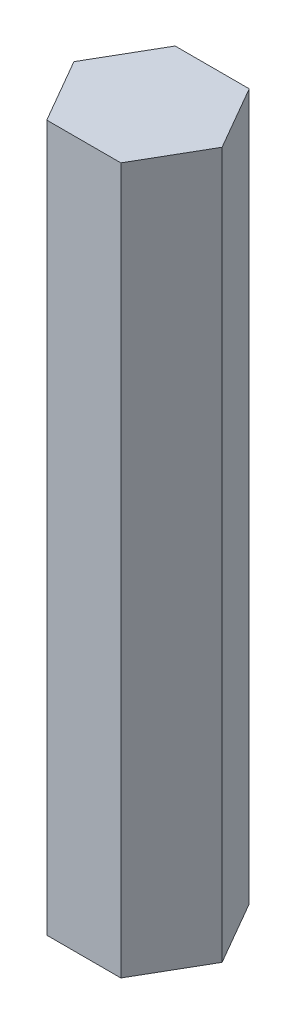
SolidWorks part; units mm, degrees
material "6061-T6 (SS)"
ref_plane "Front" through (0, 0, 0) normal (0, 0, 1) x (1, 0, 0)
ref_plane "Top" through (0, 0, 0) normal (0, 1, 0) x (1, 0, 0)
ref_plane "Right" through (0, 0, 0) normal (1, 0, 0) x (0, 0, -1)
sketch "Sketch1" plane through (0, 0, 0) normal (0, 1, 0) x (1, 0, 0)
  line L1 (7.3323, 0) -> (3.6662, 6.35)
  line L2 (3.6662, 6.35) -> (-3.6662, 6.35)
  line L3 (-3.6662, 6.35) -> (-7.3323, 0)
  line L4 (-7.3323, 0) -> (-3.6662, -6.35)
  line L5 (-3.6662, -6.35) -> (3.6662, -6.35)
  line L6 (3.6662, -6.35) -> (7.3323, 0)
  circle A0 centre (0, 0) radius 6.35 construction
  dimension "D1" = 12.7
extrude "Boss-Extrude1" add sketch "Sketch1" along normal blind 69.85
ref_axis "Axis1" through (0, 50, 0) along (0, -1, 0)
